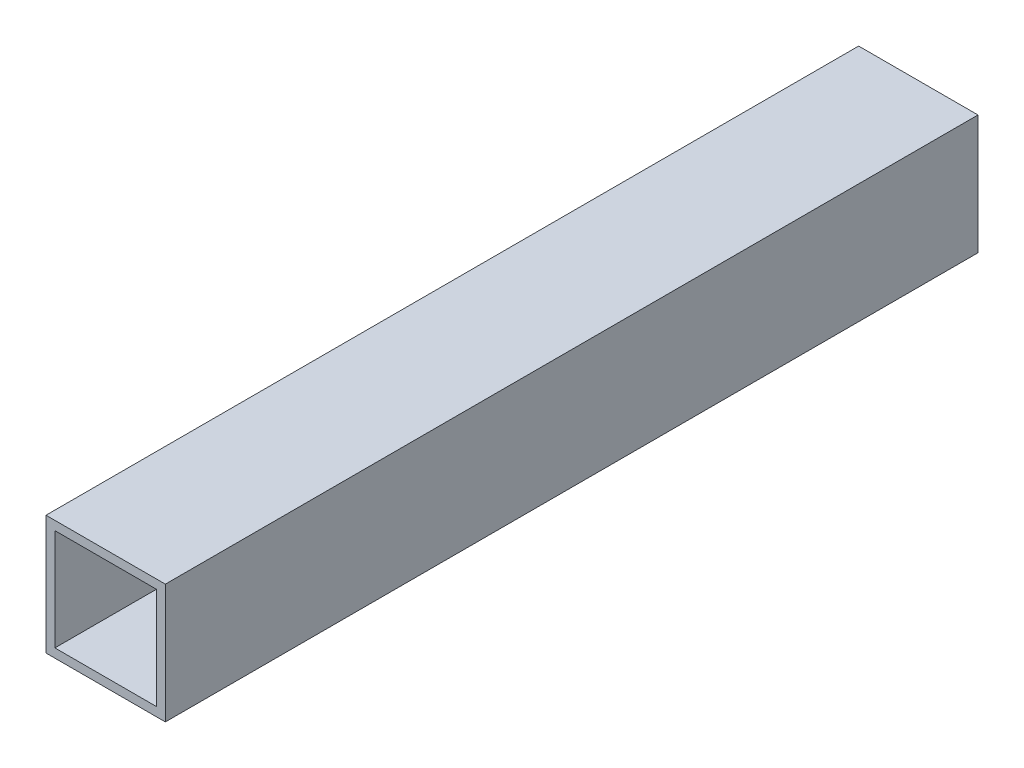
SolidWorks part; units mm, degrees
ref_plane "Plan de face" through (0, 0, 0) normal (0, 0, 1) x (1, 0, 0)
ref_plane "Plan de dessus" through (0, 0, 0) normal (0, 1, 0) x (1, 0, 0)
ref_plane "Plan de droite" through (0, 0, 0) normal (1, 0, 0) x (0, 0, -1)
sketch "Esquisse1" plane through (0, 0, 0) normal (0, 0, 1) x (1, 0, 0)
  line L1 (-11.75, -11.75) -> (11.75, -11.75)
  line L2 (-11.75, -11.75) -> (-11.75, 11.75)
  line L3 (-11.75, 11.75) -> (11.75, 11.75)
  line L4 (11.75, -11.75) -> (11.75, 11.75)
  line L5 (-11.75, -11.75) -> (11.75, 11.75) construction
  line L6 (-11.75, 11.75) -> (11.75, -11.75) construction
  line L7 (-10, -10) -> (10, -10)
  line L8 (-10, -10) -> (-10, 10)
  line L9 (-10, 10) -> (10, 10)
  line L10 (10, -10) -> (10, 10)
  line L11 (-10, -10) -> (10, 10) construction
  line L12 (-10, 10) -> (10, -10) construction
  point P1 (0, 0)
  point P6 (0, 0)
  dimension "D1" = 20
  dimension "D2" = 23.5
extrude "Boss.-Extru.1" add sketch "Esquisse1" along normal blind 160
sketch "Esquisse2" [suppressed] plane through (-11.75, 0, 0) normal (-1, 0, 0) x (0, 0, 1)
  line L0 (0, -11.75) -> (127, 11.75) construction
  line L1 (0, 11.75) -> (200, -11.75) construction
  line L2 (127, -11.75) -> (0, -11.75) construction
  circle A0 centre (63.5, 0) radius 7.2103
extrude "Enlèv. mat.-Extru.1" [suppressed] cut sketch "Esquisse2" against normal up to vertex up to point (10, -10, 0)
